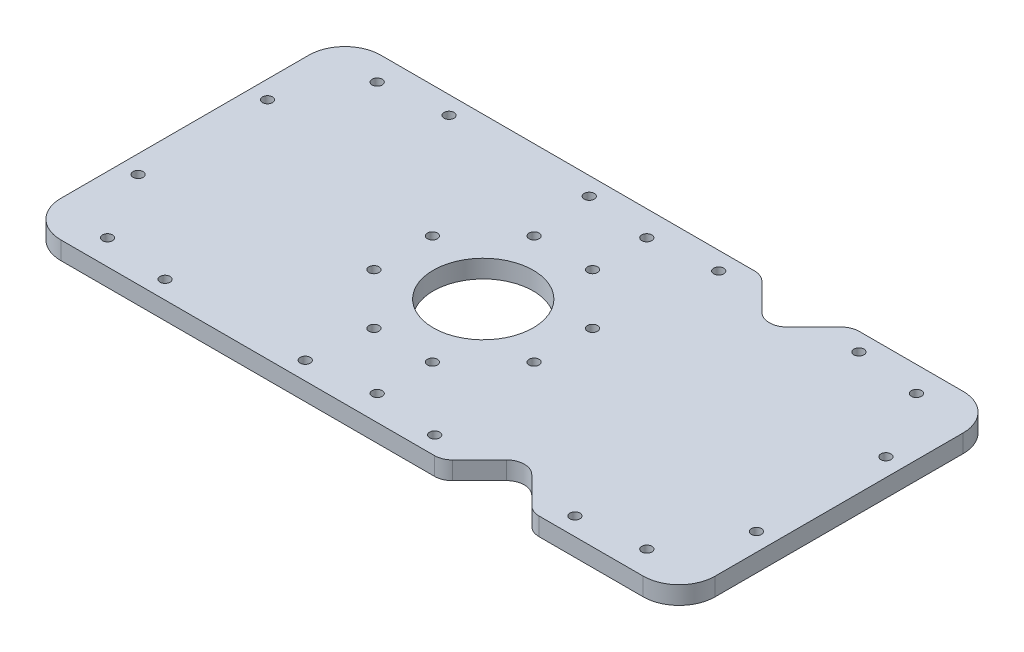
SolidWorks part; units mm, degrees
ref_plane "Front Plane" through (0, 0, 0) normal (0, 0, 1) x (1, 0, 0)
ref_plane "Top Plane" through (0, 0, 0) normal (0, 1, 0) x (1, 0, 0)
ref_plane "Right Plane" through (0, 0, 0) normal (1, 0, 0) x (0, 0, -1)
sketch "Sketch1" plane through (0, 0, 0) normal (0, 1, 0) x (1, 0, 0)
  line L0 (26.4645, -43.0355) -> (33.9645, -35.5355)
  line L1 (41.0355, -35.5355) -> (48.5355, -43.0355)
  line L2 (52.0711, -44.5) -> (81, -44.5)
  line L3 (91, -34.5) -> (91, 34.5)
  line L4 (81, 44.5) -> (52.0711, 44.5)
  line L5 (48.5355, 43.0355) -> (41.0355, 35.5355)
  line L6 (33.9645, 35.5355) -> (26.4645, 43.0355)
  line L7 (22.9289, 44.5) -> (-81, 44.5)
  line L8 (-91, 34.5) -> (-91, -34.5)
  line L9 (-81, -44.5) -> (22.9289, -44.5)
  arc A0 (22.9289, -44.5) -> (26.4645, -43.0355) centre (22.9289, -39.5) ccw
  arc A1 (41.0355, -35.5355) -> (33.9645, -35.5355) centre (37.5, -39.0711) ccw
  arc A2 (48.5355, -43.0355) -> (52.0711, -44.5) centre (52.0711, -39.5) ccw
  arc A3 (81, -44.5) -> (91, -34.5) centre (81, -34.5) ccw
  arc A4 (91, 34.5) -> (81, 44.5) centre (81, 34.5) ccw
  arc A5 (52.0711, 44.5) -> (48.5355, 43.0355) centre (52.0711, 39.5) ccw
  arc A6 (33.9645, 35.5355) -> (41.0355, 35.5355) centre (37.5, 39.0711) ccw
  arc A7 (26.4645, 43.0355) -> (22.9289, 44.5) centre (22.9289, 39.5) ccw
  arc A8 (-81, 44.5) -> (-91, 34.5) centre (-81, 34.5) ccw
  arc A9 (-91, -34.5) -> (-81, -44.5) centre (-81, -34.5) ccw
  circle A10 centre (-8, 0) radius 13.9
  circle A11 centre (-30.2739, 8.1317) radius 1.4
  circle A12 centre (-16.1317, 22.2739) radius 1.4
  circle A13 centre (0.1317, 22.2739) radius 1.4
  circle A14 centre (14.2739, 8.1317) radius 1.4
  circle A15 centre (14.2739, -8.1317) radius 1.4
  circle A16 centre (0.1317, -22.2739) radius 1.4
  circle A17 centre (-16.1317, -22.2739) radius 1.4
  circle A18 centre (-30.2739, -8.1317) radius 1.4
  circle A19 centre (-75, -37.5) radius 1.4
  circle A20 centre (-57, -39.5) radius 1.4
  circle A21 centre (-18, -39.5) radius 1.4
  circle A22 centre (0, -37.5) radius 1.4
  circle A23 centre (18, -39.5) radius 1.4
  circle A24 centre (57, -39.5) radius 1.4
  circle A25 centre (75, -37.5) radius 1.4
  circle A26 centre (86, -18) radius 1.4
  circle A27 centre (86, 18) radius 1.4
  circle A28 centre (75, 37.5) radius 1.4
  circle A29 centre (57, 39.5) radius 1.4
  circle A30 centre (18, 39.5) radius 1.4
  circle A31 centre (0, 37.5) radius 1.4
  circle A32 centre (-18, 39.5) radius 1.4
  circle A33 centre (-57, 39.5) radius 1.4
  circle A34 centre (-75, 37.5) radius 1.4
  circle A35 centre (-86, 18) radius 1.4
  circle A36 centre (-86, -18) radius 1.4
  dimension "D2" = 2.8
  dimension "D3" = 27.8
  dimension "D1" = 103.9289
extrude "Boss-Extrude1" add sketch "Sketch1" along normal blind 5
sketch "Sketch2" plane through (0, 0, 0) normal (0, 1, 0) x (1, 0, 0)
  line L0 (0, 0) -> (-142.7211, 0) construction
ref_axis "Axis1" through (-8, 0, 0) along (0, 1, 0)
